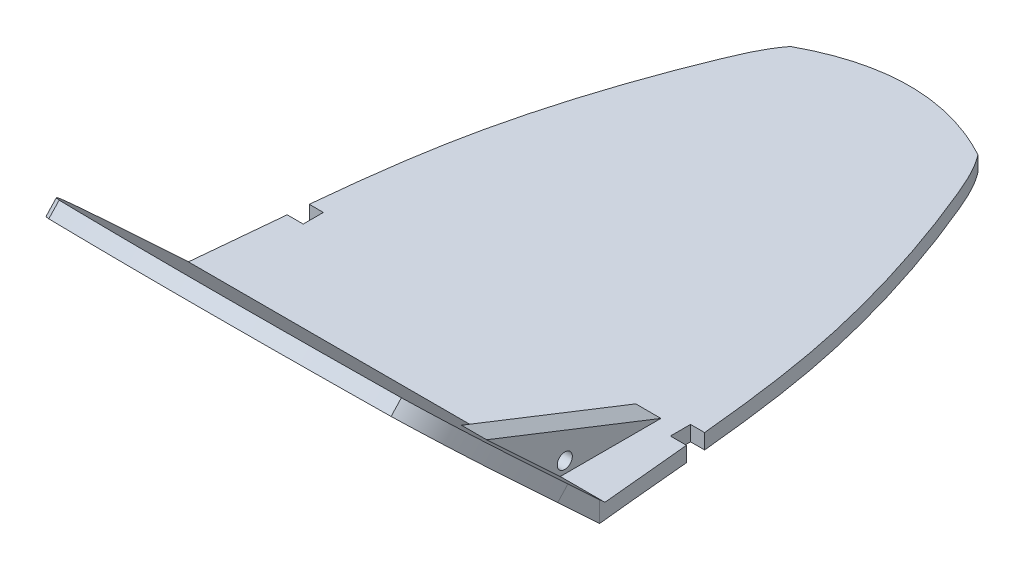
SolidWorks part; units mm, degrees
ref_plane "Front Plane" through (0, 0, 0) normal (0, 0, 1) x (1, 0, 0)
ref_plane "Top Plane" through (0, 0, 0) normal (0, 1, 0) x (1, 0, 0)
ref_plane "Right Plane" through (0, 0, 0) normal (1, 0, 0) x (0, 0, -1)
sketch "Sketch1" plane through (0, 0, 0) normal (0, 1, 0) x (1, 0, 0)
  line L0 (-48.5, 0) -> (48.5, 0)
  line L1 (0, -617.628) -> (0, 30263.7709) construction
  line L2 (-47.5, 10) -> (47.5, 10) construction
  line L3 (-46.5, 20) -> (46.5, 20) construction
  line L4 (45, 30) -> (-45, 30) construction
  line L5 (-42.5, 50) -> (42.5, 50) construction
  line L6 (40, 60) -> (-40, 60) construction
  line L7 (-1000, 112) -> (49000, 112) construction
  line L8 (-30, 90) -> (30, 90) construction
  line L9 (24, 100) -> (-24, 100) construction
  line L10 (-34.5, 80) -> (34.5, 80) construction
  line L11 (37.5, 70) -> (-37.5, 70) construction
  line L12 (48.5, 0) -> (-48.5, 0) construction
  line L13 (44, 40) -> (-44, 40) construction
  line L14 (12, 110) -> (-12, 110) construction
  line L15 (-48.5, 0) -> (-48.5, 112)
  line L16 (-48.5, 112) -> (-0.0006, 112)
  line L17 (48.5, 0) -> (48.5, 112)
  line L18 (48.5, 112) -> (0.0006, 112)
  line L19 (-12, 103.0876) -> (12, 103.0876) construction
  spline S0 degree 3 poles (-0.0006, 112) (-0.0004, 112) (-0.0002, 112) (0, 112) knots 0.499749 0.499749 0.499749 0.499749 0.5 0.5 0.5 0.5
  spline S1 degree 3 poles (-48.5, 0) (-46.6682, 16.7399) (-45.2403, 47.0287) (-35.053, 77.9764) (-30, 90) knots 0 0 0 0 0.382344 0.700509 0.700509 0.700509 0.700509
  spline S2 degree 3 poles (0.0006, 112) (0.0004, 112) (0.0002, 112) (0, 112) knots 0.499749 0.499749 0.499749 0.499749 0.5 0.5 0.5 0.5
  spline S3 degree 3 poles (48.5, 0) (46.6682, 16.7399) (45.2403, 47.0287) (35.053, 77.9764) (30, 90) knots 0 0 0 0 0.382344 0.700509 0.700509 0.700509 0.700509
  spline S4 degree 3 poles (-0.0006, 112) (-0.0004, 112) (0, 112) (0.0004, 112) (0.0006, 112) knots 0.499975 0.499975 0.499975 0.499975 0.5 0.500025 0.500025 0.500025 0.500025
  spline S5 degree 2 poles (-24, 100) (-23.9978, 100.0018) (-23.9956, 100.0036) knots 0 0 0 0.000363 0.000363 0.000363
  spline S6 degree 2 poles (-24, 100) (-23.9989, 100.0009) (-23.9978, 100.0018) knots 0 0 0 0.000045 0.000045 0.000045
  spline S8 degree 2 poles (-30, 90) (0, 116.1753) (30, 90) knots 0 0 0 1 1 1
  point P2 (0, 0)
  point P27 (0, 112)
  point P30 (0, 40)
  point P32 (0, 60)
  point P33 (0, 50)
  point P34 (0, 30)
  point P35 (0, 20)
  point P36 (0, 10)
  point P37 (0, 70)
  point P39 (0, 80)
  point P40 (0, 100)
  point P41 (0, 90)
  point P42 (0, 110)
  dimension "D2" = 47.5
  dimension "D3" = 46.5
  dimension "D4" = 45
  dimension "D5" = 44
  dimension "D6" = 42.5
  dimension "D7" = 40
  dimension "D8" = 37.5
  dimension "D9" = 34.5
  dimension "D10" = 30
  dimension "D11" = 24
  dimension "D12" = 12
  dimension "D13" = 48.5
  dimension "D14" = 10
  dimension "D15" = 20
  dimension "D16" = 30
  dimension "D17" = 40
  dimension "D18" = 50
  dimension "D19" = 60
  dimension "D20" = 70
  dimension "D21" = 80
  dimension "D22" = 90
  dimension "D23" = 100
  dimension "D24" = 110
  dimension "D25" = 112
  dimension "D26" = 24
sketch "Sketch2" plane through (0, 0, 0) normal (1, 0, 0) x (0, 0, -1)
  line L0 (0, 3) -> (-36567.6851, 34102.918) construction
  line L1 (-1000, 1.5) -> (49000, 1.5) construction
  line L3 (0, 0) -> (-36567.6851, 34099.918) construction
  line L4 (-724.1376, 679.3713) -> (35843.5474, -33420.5467) construction
  line L5 (0, 3) -> (0, 0)
  line L6 (0, 3) -> (1.1817, 3)
  line L8 (1.1817, 3) -> (-41.2368, 42.5559)
  line L9 (-41.2368, 42.5559) -> (-43.2828, 40.3618)
  line L10 (-43.2828, 40.3618) -> (0, 0)
  dimension "D1" = 43
  dimension "D2" = 43
  dimension "D3" = 3
  dimension "D4" = 58
extrude "Boss-Extrude3" add sketch "Sketch2" along normal blind 48.5 and the other way blind 48.5
sketch "Sketch3" plane through (0, 2.1941, -2.046) normal (0, 0.7314, -0.682) x (1, 0, 0)
  line L0 (0, -1000) -> (0, 49000) construction
  line L1 (-48.5, -11.1817) -> (48.5, -11.1817) construction
  line L2 (-48.5, -6.1817) -> (48.5, -6.1817) construction
  line L3 (-48.5, -16.1817) -> (48.5, -16.1817) construction
  line L4 (-48.5, -21.1817) -> (48.5, -21.1817) construction
  line L5 (-48, -26.1817) -> (48, -26.1817) construction
  line L6 (-47.5, -31.1817) -> (47.5, -31.1817) construction
  line L7 (-47, -36.1817) -> (47, -36.1817) construction
  line L8 (-46, -41.1817) -> (46, -41.1817) construction
  line L9 (-44, -46.1817) -> (44, -46.1817) construction
  line L10 (-41, -51.1817) -> (41, -51.1817) construction
  line L11 (-35, -56.1817) -> (35, -56.1817) construction
  line L12 (-48.5, -59.1817) -> (48.5, -59.1817) construction
  line L14 (-48.5, -1.1817) -> (48.5, -1.1817) construction
  line L15 (-48.5, -6.1817) -> (-48.5, -61.1817)
  line L16 (48.5, -6.1817) -> (48.5, -61.1817)
  line L17 (-48.5, -61.1817) -> (48.5, -61.1817)
  spline S0 degree 3 poles (-48.5, -6.1817) (-48.547, -9.5174) (-48.406, -14.5104) (-48.6413, -21.1971) (-47.9673, -26.1801) (-47.4883, -31.181) (-47.0773, -36.2109) (-46.1634, -41.332) (-44.0163, -46.3523) (-40.961, -51.9611) (-37.2444, -54.9103) (-35, -56.1817) knots 0 0 0 0 0.055973 0.08396 0.112086 0.140212 0.168338 0.196879 0.227022 0.259659 0.303376 0.303376 0.303376 0.303376
  spline S1 degree 2 poles (-35, -56.1817) (0, -62.1817) (35, -56.1817) knots 0 0 0 1 1 1
  spline S2 degree 3 poles (0, -59.1817) (0.0011, -59.1817) (0.0022, -59.1817) (0.0033, -59.1817) knots 0.5 0.5 0.5 0.5 0.500017 0.500017 0.500017 0.500017
  spline S3 degree 3 poles (35, -56.1817) (37.2444, -54.9103) (40.961, -51.9611) (44.0163, -46.3523) (46.1634, -41.332) (47.0773, -36.2109) (47.4883, -31.181) (47.9673, -26.1801) (48.6413, -21.1971) (48.406, -14.5104) (48.547, -9.5174) (48.5, -6.1817) knots 0.696624 0.696624 0.696624 0.696624 0.740341 0.772978 0.803121 0.831662 0.859788 0.887914 0.91604 0.944027 1 1 1 1
  point P26 (0, -56.1817)
  point P29 (0, -51.1817)
  point P30 (0, -46.1817)
  point P31 (0, -41.1817)
  point P32 (0, -36.1817)
  point P33 (0, -31.1817)
  point P34 (0, -26.1817)
  point P35 (0, -21.1817)
  point P36 (0, -16.1817)
  point P37 (0, -6.1817)
  point P38 (0, -11.1817)
  line M12 (-48.5, -59.1817) -> (48.5, -59.1817)
  line M13 (48.5, -59.1817) -> (48.5, -1.1817)
  dimension "D3" = 5
  dimension "D4" = 5
  dimension "D5" = 5
  dimension "D6" = 5
  dimension "D7" = 5
  dimension "D8" = 5
  dimension "D9" = 5
  dimension "D10" = 5
  dimension "D11" = 5
  dimension "D12" = 5
  dimension "D13" = 5
  dimension "D16" = 48
  dimension "D17" = 47.5
  dimension "D18" = 47
  dimension "D19" = 46
  dimension "D20" = 44
  dimension "D21" = 41
  dimension "D22" = 35
sketch "Sketch5" plane through (0, 0, 0) normal (0, 1, 0) x (1, 0, 0)
  line L0 (-48.5, 0) -> (48.5, 0)
  line L1 (-48.5, 0) -> (-48.5, 112)
  line L2 (48.5, 0) -> (48.5, 112)
  line L3 (-48.5, 112) -> (48.5, 112)
  dimension "D1" = 112
extrude "Boss-Extrude4" add sketch "Sketch5" along normal blind 3
extrude "Cut-Extrude2" cut sketch "Sketch1" against normal through all and the other way through all contours S1 S4 L16 L15 | L18 S4 S3 L17 region at (-47.0183, 0, -56)
extrude "Cut-Extrude4" cut sketch "Sketch3" against normal blind 3 contours S3 S1 M12 M13 | L15 L17 L16 M12 | S1 S0 L15 M12 region at (0, 43.2379, 41.9681) region at (-41.0059, 37.5217, 35.8382) region at (41.0057, 37.5216, 35.8382)
sketch "Sketch6" plane through (0, 0, 0) normal (1, 0, 0) x (0, 0, -1)
  line L0 (1.1817, -997) -> (1.1817, 49003) construction
  line L1 (-13.4453, -983.36) -> (-13.4453, 49016.64) construction
  line L2 (21.1817, -988.1669) -> (21.1817, 49011.8331) construction
  line L3 (-1013.4453, 16.64) -> (48986.5547, 16.64) construction
  line L4 (-13.4453, 16.64) -> (1.1817, 3)
  line L5 (1.1817, 3) -> (21.1817, 3)
  line L7 (90, 3) -> (1.1817, 3) construction
  line L8 (21.1817, 3) -> (-13.4453, 16.64)
  dimension "D1" = 20
extrude "Boss-Extrude5" add sketch "Sketch6" along normal blind 2.5 and the other way blind 2.5 from offset 30
sketch "Sketch7" plane through (32.5, 0, 0) normal (1, 0, 0) x (0, 0, -1)
  circle A0 centre (2.0812, 5.2759) radius 1.5
extrude "Cut-Extrude5" cut sketch "Sketch7" against normal up to next
sketch "Sketch8" plane through (0, 0, 0) normal (0, 1, 0) x (1, 0, 0)
  line L0 (-41.5, 0) -> (41.5, 0)
  line L1 (0, -617.628) -> (0, 30263.7709) construction
  line L2 (-40.5, 10) -> (40.5, 10) construction
  line L3 (-39.5, 20) -> (39.5, 20) construction
  line L4 (38, 30) -> (-38, 30) construction
  line L5 (-35.5, 50) -> (35.5, 50) construction
  line L6 (33, 60) -> (-33, 60) construction
  line L7 (-1000, 112) -> (49000, 112) construction
  line L8 (-23, 90) -> (23, 90) construction
  line L9 (17, 100) -> (-17, 100) construction
  line L10 (-27.5, 80) -> (27.5, 80) construction
  line L11 (30.5, 70) -> (-30.5, 70) construction
  line L12 (41.5, 0) -> (-41.5, 0) construction
  line L13 (37, 40) -> (-37, 40) construction
  line L14 (5, 110) -> (-5, 110) construction
  line L15 (-41.5, 0) -> (-41.5, 112)
  line L16 (-41.5, 112) -> (-0.0006, 112)
  line L17 (41.5, 0) -> (41.5, 112)
  line L18 (41.5, 112) -> (0.0006, 112)
  line L20 (-41.5, 0) -> (-54.7644, 0)
  line L21 (-41.5, 0) -> (-41.5, 112)
  line L22 (-41.5, 112) -> (-54.7644, 112)
  line L23 (-54.7644, 0) -> (-54.7644, 112)
  line L24 (41.5, 0) -> (52.946, 0)
  line L25 (41.5, 0) -> (41.5, 112)
  line L26 (41.5, 112) -> (52.946, 112)
  line L27 (52.946, 0) -> (52.946, 112)
  spline S0 degree 3 poles (-0.0006, 112) (-0.0004, 112) (-0.0002, 112) (0, 112) knots 0.499749 0.499749 0.499749 0.499749 0.5 0.5 0.5 0.5
  spline S1 degree 3 poles (-41.5, 0) (-39.6682, 16.7399) (-38.2403, 47.0287) (-26.7655, 81.888) (-20.1547, 96.5343) (-17, 100) knots 0 0 0 0 0.382344 0.700509 0.789047 0.789047 0.789047 0.789047
  spline S2 degree 3 poles (0.0006, 112) (0.0004, 112) (0.0002, 112) (0, 112) knots 0.499749 0.499749 0.499749 0.499749 0.5 0.5 0.5 0.5
  spline S3 degree 3 poles (41.5, 0) (39.6682, 16.7399) (38.2403, 47.0287) (26.7655, 81.888) (20.1547, 96.5343) (17, 100) knots 0 0 0 0 0.382344 0.700509 0.789047 0.789047 0.789047 0.789047
  spline S6 degree 2 poles (-17, 100) (0, 120) (17, 100) knots 0 0 0 1 1 1
  point P2 (0, 0)
  point P27 (0, 112)
  point P30 (0, 40)
  point P32 (0, 60)
  point P33 (0, 50)
  point P34 (0, 30)
  point P35 (0, 20)
  point P36 (0, 10)
  point P37 (0, 70)
  point P39 (0, 80)
  point P40 (0, 100)
  point P41 (0, 90)
  point P42 (0, 110)
  dimension "D2" = 40.5
  dimension "D3" = 39.5
  dimension "D4" = 38
  dimension "D5" = 37
  dimension "D6" = 35.5
  dimension "D7" = 33
  dimension "D8" = 30.5
  dimension "D9" = 27.5
  dimension "D10" = 23
  dimension "D11" = 17
  dimension "D12" = 5
  dimension "D13" = 41.5
  dimension "D14" = 10
  dimension "D15" = 20
  dimension "D16" = 30
  dimension "D17" = 40
  dimension "D18" = 50
  dimension "D19" = 60
  dimension "D20" = 70
  dimension "D21" = 80
  dimension "D22" = 90
  dimension "D23" = 100
  dimension "D24" = 110
  dimension "D25" = 112
extrude "Cut-Extrude6" cut sketch "Sketch8" against normal through all both and the other way through all contours L23 L20 L15 L22 | L24 L27 L26 L17 | S1 S6 S3 L17 L18 S2 S0 L16 L15 region at (-48.1322, 0, -56) region at (-40.106, 0, -56) region at (47.223, 0, -56)
sketch "Sketch9" plane through (0, -0.8896, -0.954) normal (0, -0.7314, 0.682) x (1, 0, 0)
  line L0 (0, -1000) -> (0, 49000) construction
  line L1 (41.5, 12.6975) -> (-41.5, 12.6975) construction
  line L3 (41.5, 17.6975) -> (-41.5, 17.6975) construction
  line L4 (41.5, 22.6975) -> (-41.5, 22.6975) construction
  line L5 (41.5, 27.6975) -> (-41.5, 27.6975) construction
  line L6 (41, 32.6975) -> (-41, 32.6975) construction
  line L7 (40, 37.6975) -> (-40, 37.6975) construction
  line L8 (38, 42.6975) -> (-38, 42.6975) construction
  line L9 (34, 47.6975) -> (-34, 47.6975) construction
  line L10 (34, 52.6975) -> (-34, 52.6975) construction
  line L11 (27, 57.6975) -> (-27, 57.6975) construction
  line L12 (-41.5, 1.3044) -> (-55.1837, 1.3044)
  line L13 (-41.5, 1.3044) -> (-41.5, 62.4183)
  line L14 (-41.5, 62.4183) -> (-55.1837, 62.4183)
  line L15 (41.5, 1.3044) -> (-41.5, 1.3044) construction
  line L16 (-55.1837, 1.3044) -> (-55.1837, 62.4183)
  line L17 (48.5, 62.4183) -> (-48.5, 62.4183)
  line L18 (41.5, 1.3044) -> (52.4108, 1.3044)
  line L19 (41.5, 1.3044) -> (41.5, 62.4183)
  line L20 (41.5, 62.4183) -> (52.4108, 62.4183)
  line L21 (52.4108, 1.3044) -> (52.4108, 62.4183)
  spline S0 degree 3 poles (-34, 47.6975) (-37.0897, 45.0948) (-40.4826, 38.3871) (-42.3149, 22.2553) (-41.1303, 10.109) (-41.5, 1.3044) knots 0 0 0 0 0.244098 0.453483 1 1 1 1
  spline S1 degree 3 poles (0, 57.6975) (0.0001, 57.6975) (0.0002, 57.6975) (0.0003, 57.6975) knots 0.5 0.5 0.5 0.5 0.500004 0.500004 0.500004 0.500004
  spline S2 degree 3 poles (0, 60.4183) (-0.0011, 60.4183) (-0.0022, 60.4183) (-0.0033, 60.4183) knots 0.5 0.5 0.5 0.5 0.500017 0.500017 0.500017 0.500017
  spline S3 degree 3 poles (0, 57.6975) (0.0002, 57.6975) (0.0004, 57.6975) (0.0006, 57.6975) knots 0.5 0.5 0.5 0.5 0.500003 0.500003 0.500003 0.500003
  spline S4 degree 3 poles (34, 47.6975) (37.0897, 45.0948) (40.4826, 38.3871) (42.3149, 22.2553) (41.1303, 10.109) (41.5, 1.3044) knots 0 0 0 0 0.244098 0.453483 1 1 1 1
  spline S5 degree 2 poles (-34, 47.6975) (0, 57.6975) (34, 47.6975) knots 0 0 0 1 1 1
  point P26 (0, 57.6975)
  point P29 (0, 52.6975)
  point P30 (0, 47.6975)
  point P31 (0, 42.6975)
  point P32 (0, 37.6975)
  point P33 (0, 32.6975)
  point P34 (0, 27.6975)
  point P35 (0, 22.6975)
  point P36 (0, 17.6975)
  point P37 (0, 7.6975)
  point P38 (0, 12.6975)
  spline M55 degree 2 poles (-35, 57.4862) (0, 63.4862) (35, 57.4862) knots 0 0 0 1 1 1 only from (0, 60.4862) to (-35, 57.4862)
  spline M56 degree 3 poles (-35, 57.4862) (-37.2444, 56.2147) (-40.961, 53.2655) (-44.0163, 47.6567) (-46.1634, 42.6364) (-47.0773, 37.5153) (-47.4883, 32.4854) (-47.9673, 27.4846) (-48.6413, 22.5015) (-48.406, 15.8148) (-48.547, 10.8218) (-48.5, 7.4862) knots 0 0 0 0 0.043716 0.076354 0.106497 0.135037 0.163164 0.19129 0.219416 0.247402 0.303376 0.303376 0.303376 0.303376 only from (-35, 57.4862) to (-48.5, 22.4862)
  line M57 (-48.5, 22.4862) -> (-48.5, 1.3044)
  line M58 (-48.5, 1.3044) -> (-41.5, 1.3044)
  line M60 (41.5, 1.3044) -> (48.5, 1.3044)
  line M61 (48.5, 1.3044) -> (48.5, 22.4862)
  spline M62 degree 3 poles (48.5, 7.4862) (48.547, 10.8218) (48.406, 15.8148) (48.6413, 22.5015) (47.9673, 27.4846) (47.4883, 32.4854) (47.0773, 37.5153) (46.1634, 42.6364) (44.0163, 47.6567) (40.961, 53.2655) (37.2444, 56.2147) (35, 57.4862) knots 0.696624 0.696624 0.696624 0.696624 0.752598 0.780584 0.80871 0.836836 0.864963 0.893503 0.923646 0.956284 1 1 1 1 only from (48.5, 22.4862) to (35, 57.4862)
  spline M63 degree 2 poles (-35, 57.4862) (0, 63.4862) (35, 57.4862) knots 0 0 0 1 1 1 only from (35, 57.4862) to (0.0033, 60.4862)
  line M64 (0.0033, 60.4862) -> (0, 60.4862)
  dimension "D3" = 83
  dimension "D5" = 5
  dimension "D6" = 5
  dimension "D7" = 5
  dimension "D8" = 5
  dimension "D9" = 5
  dimension "D10" = 5
  dimension "D11" = 5
  dimension "D12" = 5
  dimension "D13" = 5
  dimension "D14" = 83
  dimension "D15" = 83
  dimension "D16" = 41.5
  dimension "D17" = 41
  dimension "D18" = 40
  dimension "D19" = 38
  dimension "D20" = 34
  dimension "D21" = 34
  dimension "D22" = 27
extrude "Cut-Extrude7" cut sketch "Sketch9" against normal through all both and the other way through all contours L16 L12 L13 L14 M57 M56 | L19 L17 L13 M62 M56 M55 M64 M63 | L18 L21 L20 L17 L19 M62 M61 | S1 L19 L13 | L19 M60 M61 M62 | L13 M58 M56 M57 region at (-48.3539, 20.8532, 22.3623) region at (0, 36.7487, 39.4082) region at (46.9674, 20.8566, 22.366)
sketch "Sketch10" plane through (0, 3, 0) normal (0, 1, 0) x (1, 0, 0)
  line L0 (0, -1000) -> (0, 49000) construction
  line L1 (-1000, 103.0876) -> (49000, 103.0876) construction
  line L2 (-1000, 21.0876) -> (49000, 21.0876) construction
  line L3 (36.4704, 23.0876) -> (42.4704, 19.0876) construction
  line L4 (-36.4704, 19.0876) -> (-42.4704, 19.0876)
  line L5 (-36.4704, 19.0876) -> (-36.4704, 23.0876)
  line L6 (-36.4704, 23.0876) -> (-42.4704, 23.0876)
  line L7 (-42.4704, 19.0876) -> (-42.4704, 23.0876)
  line L8 (-36.4704, 19.0876) -> (-42.4704, 23.0876) construction
  line L9 (-36.4704, 23.0876) -> (-42.4704, 19.0876) construction
  line L10 (36.4704, 19.0876) -> (42.4704, 23.0876) construction
  line L11 (42.4704, 19.0876) -> (42.4704, 23.0876)
  line L12 (36.4704, 23.0876) -> (42.4704, 23.0876)
  line L13 (36.4704, 19.0876) -> (36.4704, 23.0876)
  line L14 (36.4704, 19.0876) -> (42.4704, 19.0876)
  spline S0 degree 3 poles (-18.634, 98.0383) (-20.7042, 95.3086) (-27.0118, 81.1396) (-38.1094, 47.4263) (-39.6301, 17.5182) (-41.3724, 1.1817) knots 0.009 0.009 0.009 0.009 0.080599 0.398764 0.772109 0.772109 0.772109 0.772109 construction
  point P6 (-39.4704, 21.0876)
  point P18 (39.4704, 21.0876)
  dimension "D1" = 82
  dimension "D2" = 4
  dimension "D3" = 6
extrude "Cut-Extrude8" cut sketch "Sketch10" against normal through all both and the other way through all
